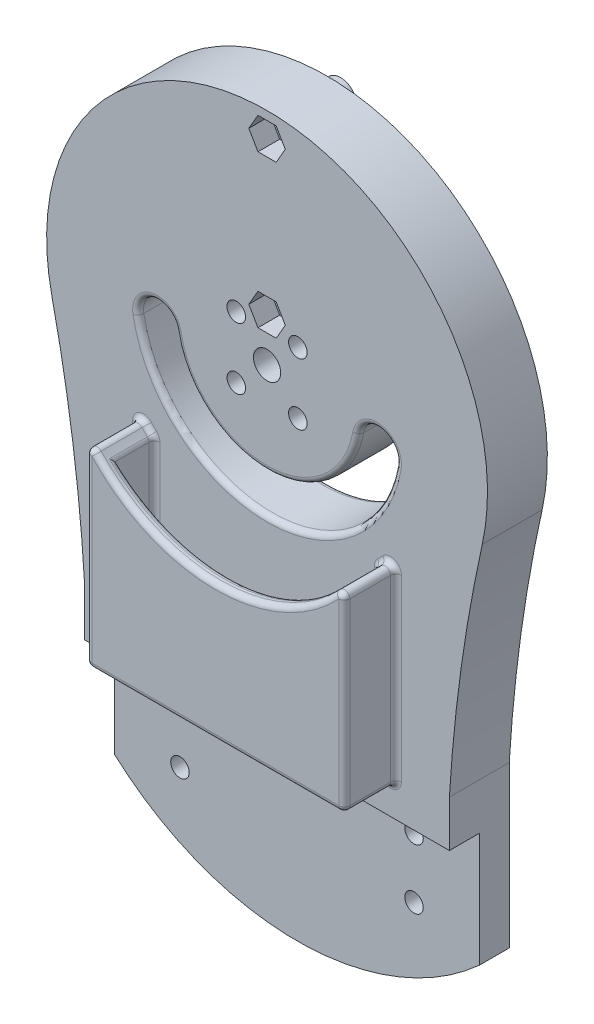
SolidWorks part; units mm, degrees
ref_plane "Front Plane" through (0, 0, 0) normal (0, 0, 1) x (1, 0, 0)
ref_plane "Top Plane" through (0, 0, 0) normal (0, 1, 0) x (1, 0, 0)
ref_plane "Right Plane" through (0, 0, 0) normal (1, 0, 0) x (0, 0, -1)
sketch "Sketch1" plane through (0, 0, 0) normal (0, 0, 1) x (1, 0, 0)
  line L0 (0, 0) -> (0, -52) construction
  line L1 (-33.5, -81.5) -> (33.5, -81.5)
  line L2 (-33.5, -81.5) -> (-33.5, -52)
  line L3 (-33.5, -52) -> (33.5, -52)
  line L4 (33.5, -81.5) -> (33.5, -52)
  line L5 (-33.5, -81.5) -> (33.5, -52) construction
  line L6 (-33.5, -52) -> (33.5, -81.5) construction
  line L7 (-55.7233, -60.5) -> (56.1574, -60.5) construction
  line L8 (0, 0) -> (-5.6569, -5.6569)
  circle A0 centre (0, 0) radius 40.5
  circle A1 centre (0, 0) radius 2.5
  arc A4 (-33.5, -52) -> (-39.5426, -8.7542) centre (-309.506, -68.5201) ccw
  arc A5 (33.5, -52) -> (39.5426, -8.7542) centre (309.506, -68.5201) cw
  arc A7 (-33.5, -81.5) -> (33.5, -81.5) centre (0, -44.3819) ccw
  circle A8 centre (0, 0) radius 8 construction
  circle A13 centre (-5.6569, -5.6569) radius 1.7
  circle A14 centre (-5.6569, 5.6569) radius 1.7
  circle A15 centre (5.6569, 5.6569) radius 1.7
  circle A16 centre (5.6569, -5.6569) radius 1.7
  point P4 (0, -66.75)
  point P37 (0, 0)
  dimension "D1" = 81
  dimension "D2" = 5
  dimension "D6" = 8.5
  dimension "D8" = 16
  dimension "D9" = 3.4
  dimension "D10" = 3.4
  dimension "D11" = 3.4
  dimension "D14" = 3.4
  dimension "D3" = 52
  dimension "D4" = 67
  dimension "D5" = 29.5
  dimension "D7" = 60.5
  dimension "D13" = 45
  dimension "D15" = 4
extrude "Boss-Extrude1" add sketch "Sketch1" along normal blind 5.5 and the other way blind 5.5 contours A0 A1 | L3 A0 | L1 L3 | L1 A7 region at (0, -66.75, 0) region at (0, -86.7143, 0) region at (0, -41.5421, 0) region at (-4.2786, 39.1212, 0)
sketch "Sketch2" plane through (0, 0, 5.5) normal (0, 0, 1) x (1, 0, 0)
  line L0 (-33.5, -81.5) -> (33.5, -81.5)
  line L1 (-33.5, -81.5) -> (-33.5, -60.5)
  line L2 (33.5, -81.5) -> (33.5, -60.5)
  line L3 (-33.5, -60.5) -> (33.5, -60.5)
  line L4 (-33.5, -81.5) -> (-33.5, -52) construction
  line L5 (33.5, -81.5) -> (33.5, -52) construction
  circle A0 centre (-21.5, -77.5) radius 1.7
  circle A1 centre (21.5, -77.5) radius 1.7
  circle A2 centre (21.5, -66.5) radius 1.7
  circle A3 centre (-21.5, -66.5) radius 1.7
  dimension "D2" = 3.4
  dimension "D3" = 3.4
  dimension "D4" = 3.4
  dimension "D5" = 3.4
  dimension "D8" = 6
  dimension "D1" = 21
  dimension "D6" = 12
  dimension "D7" = 12
  dimension "D9" = 11
  dimension "D10" = 67
  dimension "D11" = 81.5
  dimension "D12" = 33.5
extrude "Cut-Extrude1" cut sketch "Sketch2" against normal through all contours A0 | A3 | A2 | A1
sketch "Sketch3" plane through (0, 0, 5.5) normal (0, 0, 1) x (1, 0, 0)
  line L0 (33.5, -81.5) -> (33.5, -52) construction
  line L1 (-33.5, -95.5) -> (33.5, -95.5)
  line L2 (-33.5, -95.5) -> (-33.5, -60.5)
  line L3 (-33.5, -60.5) -> (33.5, -60.5)
  line L4 (33.5, -95.5) -> (33.5, -60.5)
  dimension "D1" = 35
  dimension "D2" = 60.5
  dimension "D3" = 33.5
  dimension "D4" = 67
extrude "Cut-Extrude2" cut sketch "Sketch3" against normal blind 5.5
sketch "Sketch4" plane through (0, 0, -5.5) normal (0, 0, -1) x (-1, 0, 0)
  circle A0 centre (0, 0) radius 4.7825 construction
  circle A2 centre (0, 36) radius 1.7
  circle A3 centre (0, 8) radius 1.7
  circle A5 centre (0, 36) radius 4 construction
  dimension "D4" = 3.4
  dimension "D5" = 3.4
  dimension "D6" = 8
  dimension "D1" = 8
  dimension "D2" = 28
extrude "Cut-Extrude3" cut sketch "Sketch4" against normal through all
sketch "Sketch5" plane through (0, 0, 5.5) normal (0, 0, 1) x (1, 0, 0)
  line L0 (-1.675, 10.9012) -> (1.675, 10.9012)
  line L1 (1.675, 10.9012) -> (3.35, 8)
  line L2 (-1.675, 10.9012) -> (-3.35, 8)
  line L3 (-3.35, 8) -> (-1.675, 5.0988)
  line L4 (-1.675, 5.0988) -> (1.675, 5.0988)
  line L5 (1.675, 5.0988) -> (3.35, 8)
  line L6 (-1.675, 10.9012) -> (0, 8) construction
  line L7 (0, 8) -> (1.675, 10.9012) construction
  line L8 (0, 8) -> (-1.675, 5.0988) construction
  line L9 (0, 8) -> (1.675, 5.0988) construction
  line L10 (-3.35, 8) -> (3.35, 8) construction
  line L11 (-9.1797, 22) -> (14.4985, 22) construction
  line L12 (-1.675, 38.9012) -> (1.675, 38.9012)
  line L13 (-3.35, 36) -> (-1.675, 38.9012)
  line L14 (-1.675, 33.0988) -> (-3.35, 36)
  line L15 (-1.675, 33.0988) -> (1.675, 33.0988)
  line L16 (1.675, 33.0988) -> (3.35, 36)
  line L17 (1.675, 38.9012) -> (3.35, 36)
  circle A0 centre (0, 8) radius 3.35 construction
  circle A1 centre (0, 36) radius 3.35 construction
  dimension "D1" = 6.7
  dimension "D6" = 6.7
  dimension "D2" = 60
  dimension "D3" = 60
  dimension "D4" = 60
  dimension "D5" = 14
extrude "Cut-Extrude4" cut sketch "Sketch5" against normal blind 4 contours L5 L1 L0 L2 L3 L4 | L16 L17 L12 L13 L14 L15
ref_plane "Plane1" through (33.5, -81.5, -5.5) normal (0, 0, 1) x (1, 0, 0)
sketch "Sketch6" plane through (33.5, -81.5, -5.5) normal (0, 0, 1) x (1, 0, 0)
  line L0 (-26.1681, 90.058) -> (-29.5181, 84.2557) construction
  line L1 (-26.1681, 84.2557) -> (-29.5181, 90.058) construction
  line L2 (-24.4931, 87.1569) -> (-31.1931, 87.1569) construction
  line L3 (-26.1681, 90.058) -> (-24.4931, 87.1569)
  line L4 (-24.4931, 87.1569) -> (-26.1681, 84.2557)
  line L5 (-26.1681, 84.2557) -> (-29.5181, 84.2557)
  line L6 (-29.5181, 84.2557) -> (-31.1931, 87.1569)
  line L7 (-31.1931, 87.1569) -> (-29.5181, 90.058)
  line L8 (-29.5181, 90.058) -> (-26.1681, 90.058)
  line L9 (-27.8431, 75.8431) -> (-39.1569, 87.1569) construction
  line L10 (-27.8431, 87.1569) -> (-39.1569, 75.8431) construction
  line L11 (-35.8069, 87.1569) -> (-42.5069, 87.1569) construction
  line L12 (-39.1569, 87.1569) -> (-37.4819, 90.058) construction
  line L13 (-39.1569, 87.1569) -> (-40.8319, 90.058) construction
  line L14 (-39.1569, 87.1569) -> (-37.4819, 84.2557) construction
  line L15 (-39.1569, 87.1569) -> (-40.8319, 84.2557) construction
  line L22 (-37.4819, 84.2557) -> (-35.8069, 87.1569)
  line L23 (-35.8069, 87.1569) -> (-37.4819, 90.058)
  line L24 (-37.4819, 90.058) -> (-40.8319, 90.058)
  line L25 (-40.8319, 90.058) -> (-42.5069, 87.1569)
  line L26 (-42.5069, 87.1569) -> (-40.8319, 84.2557)
  line L27 (-40.8319, 84.2557) -> (-37.4819, 84.2557)
  line L28 (-39.1569, 79.1931) -> (-42.058, 77.5181)
  line L29 (-36.2557, 77.5181) -> (-39.1569, 79.1931)
  line L30 (-36.2557, 74.1681) -> (-36.2557, 77.5181)
  line L31 (-39.1569, 72.4931) -> (-36.2557, 74.1681)
  line L32 (-42.058, 74.1681) -> (-39.1569, 72.4931)
  line L33 (-42.058, 77.5181) -> (-42.058, 74.1681)
  line L34 (-27.8431, 72.4931) -> (-30.7443, 74.1681)
  line L35 (-24.942, 74.1681) -> (-27.8431, 72.4931)
  line L36 (-24.942, 77.5181) -> (-24.942, 74.1681)
  line L37 (-27.8431, 79.1931) -> (-24.942, 77.5181)
  line L38 (-30.7443, 77.5181) -> (-27.8431, 79.1931)
  line L39 (-30.7443, 74.1681) -> (-30.7443, 77.5181)
  line L40 (-10.325, 12.0988) -> (-13.675, 17.9012) construction
  line L41 (-10.325, 17.9012) -> (-13.675, 12.0988) construction
  line L42 (-8.65, 15) -> (-15.35, 15) construction
  line L43 (-10.325, 6.9012) -> (-13.675, 1.0988) construction
  line L44 (-10.325, 1.0988) -> (-13.675, 6.9012) construction
  line L45 (-8.65, 4) -> (-15.35, 4) construction
  line L46 (-33.5, 21.3433) -> (-33.5, -3.4407) construction
  line L47 (-8.65, 4) -> (-10.325, 6.9012)
  line L48 (-10.325, 6.9012) -> (-13.675, 6.9012)
  line L49 (-13.675, 6.9012) -> (-15.35, 4)
  line L50 (-15.35, 4) -> (-13.675, 1.0988)
  line L51 (-13.675, 1.0988) -> (-10.325, 1.0988)
  line L52 (-10.325, 1.0988) -> (-8.65, 4)
  line L53 (-10.325, 17.9012) -> (-13.675, 17.9012)
  line L54 (-13.675, 17.9012) -> (-15.35, 15)
  line L55 (-15.35, 15) -> (-13.675, 12.0988)
  line L56 (-13.675, 12.0988) -> (-10.325, 12.0988)
  line L57 (-10.325, 12.0988) -> (-8.65, 15)
  line L58 (-8.65, 15) -> (-10.325, 17.9012)
  line L59 (-53.325, 1.0988) -> (-56.675, 1.0988)
  line L60 (-51.65, 4) -> (-53.325, 1.0988)
  line L61 (-53.325, 6.9012) -> (-51.65, 4)
  line L62 (-56.675, 6.9012) -> (-53.325, 6.9012)
  line L63 (-58.35, 4) -> (-56.675, 6.9012)
  line L64 (-56.675, 1.0988) -> (-58.35, 4)
  line L65 (-56.675, 12.0988) -> (-58.35, 15)
  line L66 (-53.325, 12.0988) -> (-56.675, 12.0988)
  line L67 (-51.65, 15) -> (-53.325, 12.0988)
  line L68 (-53.325, 17.9012) -> (-51.65, 15)
  line L69 (-56.675, 17.9012) -> (-53.325, 17.9012)
  line L70 (-58.35, 15) -> (-56.675, 17.9012)
  circle A0 centre (-33.5, 81.5) radius 8 construction
  circle A1 centre (-27.8431, 87.1569) radius 3.35 construction
  circle A3 centre (-39.1569, 87.1569) radius 3.35 construction
  circle A4 centre (-12, 15) radius 3.35 construction
  circle A5 centre (-12, 4) radius 3.35 construction
  circle A7 centre (-55, 4) radius 3.35 construction
  dimension "D1" = 6.7
  dimension "D5" = 6.7
  dimension "D9" = 6.7
  dimension "D10" = 6.7
  dimension "D11" = 60
  dimension "D17" = 6.7
  dimension "D2" = 60
  dimension "D3" = 60
  dimension "D4" = 60
  dimension "D6" = 60
  dimension "D7" = 60
  dimension "D8" = 60
  dimension "D12" = 60
  dimension "D13" = 60
  dimension "D14" = 60
  dimension "D15" = 21.5
  dimension "D16" = 43
extrude "Cut-Extrude7" cut sketch "Sketch6" along normal blind 3 contours L8 L3 L4 L5 L6 L7 | L27 L22 L23 L24 L25 L26 | L28 L33 L32 L31 L30 L29 | L34 L39 L38 L37 L36 L35 | L59 L64 L63 L62 L61 L60 | L65 L70 L69 L68 L67 L66 | L52 L47 L48 L49 L50 L51 | L58 L53 L54 L55 L56 L57
sketch "Sketch7" plane through (0, 0, -5.5) normal (0, 0, -1) x (-1, 0, 0)
  circle A0 centre (0, 8) radius 3
  circle A1 centre (0, 36) radius 3
  circle A2 centre (0, 36) radius 1.7
  circle A3 centre (0, 8) radius 1.7
  dimension "D1" = 6
  dimension "D2" = 6
  dimension "D3" = 3.4
  dimension "D4" = 3.4
extrude "Boss-Extrude2" add sketch "Sketch7" along normal blind 2.5
sketch "Sketch9" plane through (0, 0, -5.5) normal (0, 0, -1) x (-1, 0, 0)
  line L0 (-2.7293, 4) -> (2.7293, 4)
  line L1 (-11.5, 2.2) -> (11.5, 2.2)
  line L2 (-11.5, 2.2) -> (-11.5, -2.2)
  line L3 (-11.5, -2.2) -> (11.5, -2.2)
  line L4 (11.5, 2.2) -> (11.5, -2.2)
  line L5 (-11.5, 2.2) -> (11.5, -2.2) construction
  line L6 (-11.5, -2.2) -> (11.5, 2.2) construction
  circle A0 centre (0, 0) radius 4.8424
  circle A1 centre (0, 0) radius 2.5
  dimension "D3" = 4
  dimension "D1" = 4.4
  dimension "D2" = 23
extrude "Boss-Extrude3" add sketch "Sketch9" along normal blind 8 contours A0 L1 L2 L3 | A0 L3 L4 L1 | A1 L3 A0 L1 | A1 L1 A0 L3 | A1 L1 A0 | A1 L3 A0 region at (0, 3.0636, -5.5) region at (8.0833, 0, -5.5) region at (3.3746, 0, -5.5) region at (-3.3746, 0, -5.5) region at (-8.0833, 0, -5.5) region at (0, -3.3158, -5.5)
sketch "Sketch10" plane through (0, 0, -13.5) normal (0, 0, -1) x (-1, 0, 0)
  line L0 (4.3138, 2.2) -> (11.5, 2.2) construction
  line L1 (-14.44, 28.2) -> (14.4114, 28.2) construction
  line L2 (-14.44, 22.2) -> (14.8305, 22.2) construction
  line L3 (4.3138, 2.2) -> (11.5, 2.2) construction
  line L4 (-13.3353, 25.2) -> (9.1762, 25.2) construction
  circle A1 centre (0, 0) radius 25.2 construction
  dimension "D1" = 20
  dimension "D2" = 26
  dimension "D3" = 3
sketch "Sketch11" plane through (0, 0, -5.5) normal (0, 0, -1) x (-1, 0, 0)
  line L0 (-24, 0) -> (24, 0)
  line L1 (0, 0) -> (0, -17) construction
  circle A0 centre (0, 0) radius 17
  circle A1 centre (0, 0) radius 24
  circle A3 centre (0, 0) radius 20.5 construction
  circle A5 centre (-20.199, -3.5) radius 3.5
  circle A6 centre (20.199, -3.5) radius 3.5
  dimension "D1" = 34
  dimension "D2" = 7
  dimension "D3" = 3.5
  dimension "D5" = 7
extrude "Cut-Extrude8" cut sketch "Sketch11" against normal through all contours A1 A6 A0 A5 | A5 | A6 A1 region at (20.199, -3.5, -5.5) region at (19.8548, -7.5031, -5.5) region at (-20.199, -3.5, -5.5)
sketch "Sketch12" plane through (0, 0, 5.5) normal (0, 0, 1) x (1, 0, 0)
  line L0 (-23.699, -3.5) -> (-23.699, -55)
  line L1 (23.699, -3.5) -> (23.699, -55)
  line L2 (23.699, -55) -> (-23.699, -55)
  line L3 (0, 0) -> (0, -30) construction
  line L4 (0, -30) -> (0, -55)
  circle A0 centre (0, 0) radius 30
  arc A1 (-16.7504, -2.9024) -> (-23.6476, -4.0976) centre (-20.199, -3.5) ccw construction
  arc A2 (23.6476, -4.0976) -> (16.7504, -2.9024) centre (20.199, -3.5) ccw construction
  circle A3 centre (-20.199, -3.5) radius 3.5 construction
  circle A4 centre (20.199, -3.5) radius 3.5 construction
  dimension "D1" = 60
  dimension "D2" = 47.398
  dimension "D3" = 25
extrude "Boss-Extrude4" add sketch "Sketch12" along normal blind 9.5 contours A0 L0 L2 L4 | A0 L4 L2 L1 region at (-12.61, -40.552, 5.5) region at (12.61, -40.552, 5.5)
fillet "Fillet1" radius 1 8 edges at (23.699, -18.3945, 10.25) (-23.699, -18.3945, 10.25) (23.699, -55, 10.25) (-23.699, -55, 10.25) (0, -30, 15) (23.699, -36.6972, 15) (-23.699, -36.6972, 15) (0, -55, 15)
sketch "Sketch13" plane through (0, -55, 0) normal (0, -1, 0) x (1, 0, 0)
  line L0 (33.5, 5.5) -> (-33.5, 5.5) construction
  line L1 (-20.699, 5.5) -> (20.699, 5.5)
  line L2 (-20.699, 5.5) -> (-20.699, 12.5)
  line L3 (-20.699, 12.5) -> (20.699, 12.5)
  line L4 (20.699, 5.5) -> (20.699, 12.5)
  line L5 (-23.699, 5.5) -> (-23.699, 14) construction
  line L6 (22.699, 15) -> (-22.699, 15) construction
  line L7 (23.699, 14) -> (23.699, 5.5) construction
  dimension "D1" = 3
  dimension "D2" = 2.5
  dimension "D3" = 3
extrude "Cut-Extrude9" cut sketch "Sketch13" against normal through all contours L2 L1 L4 L3
fillet "Fillet2" radius 1 26 edges at (-21.3425, -21.0831, 5.5) (-23.0649, -20.1823, 5.5) (-23.699, -37.5565, 5.5) (-23.4061, -54.7071, 5.5) (21.3425, -21.0831, 5.5) (23.0649, -20.1823, 5.5) (23.699, -37.5565, 5.5) (23.4061, -54.7071, 5.5) (20.699, -21.7152, 9) (0, -30, 12.5) (-20.699, -21.7152, 9) (-20.699, -55, 9) (20.699, -55, 9) (0, -55, 12.5) (-21.699, -55, 5.5) (21.699, -55, 5.5) (20.699, -38.3576, 5.5) (-20.699, -38.3576, 5.5) (20.7966, -0.0514, -5.5) (0, -17, -5.5) (-20.7966, -0.0514, -5.5) (20.7966, -0.0514, 5.5) (0, -17, 5.5) (-20.7966, -0.0514, 5.5) (0, -24, -5.5) (0, -24, 5.5)
sketch "Sketch14" plane through (0, 0, -5.5) normal (0, 0, -1) x (-1, 0, 0)
  line L0 (0, 0) -> (-13.4234, -7.75)
  line L1 (0, 0) -> (0, -15.5) construction
  line L2 (0, 0) -> (13.4234, -7.75)
  circle A0 centre (0, 0) radius 15.5
  circle A1 centre (0, 0) radius 12.5
  dimension "D1" = 31
  dimension "D2" = 3
  dimension "D3" = 60
  dimension "D4" = 60
extrude "Boss-Extrude5" add sketch "Sketch14" along normal blind 20 contours L1 A1 L0 A0 | A1 L1 A0 L2 region at (6.7101, -11.6222, -5.5) region at (-6.7101, -11.6222, -5.5)
sketch "Sketch15" plane through (0, 0, -5.5) normal (0, 0, -1) x (-1, 0, 0)
  line L0 (0, 0) -> (0, 18.9061) construction
  line L1 (0, 0) -> (-32.3633, 3.9737)
  line L2 (0, 0) -> (-28.6359, 14.5907)
  circle A0 centre (0, 0) radius 12.5
  circle A1 centre (0, 0) radius 30
  circle A2 centre (0, 0) radius 28
  circle A3 centre (0, 0) radius 14.5
  dimension "D1" = 60
  dimension "D2" = 25
  dimension "D5" = 2
  dimension "D6" = 2
  dimension "D3" = 63
  dimension "D4" = 83
extrude "Boss-Extrude6" add sketch "Sketch15" along normal blind 4 contours A2 L2 A1 L1 | L2 A3 L1 A0 region at (12.8682, 3.9342, -5.5) region at (27.6032, 8.4391, -5.5)
sketch "Sketch16" plane through (0, 0, -9.5) normal (0, 0, -1) x (-1, 0, 0)
  line L0 (-29.7764, 3.6561) -> (0, 0)
  line L1 (0, 0) -> (-26.7302, 13.6197)
  circle A0 centre (0, 0) radius 12.5
  circle A1 centre (0, 0) radius 30
  arc M3 (-27.7913, 3.4123) -> (-24.9482, 12.7117) centre (0, 0) cw
  line M4 (-24.9482, 12.7117) -> (-26.7302, 13.6197)
  arc M5 (-26.7302, 13.6197) -> (-29.7764, 3.6561) centre (0, 0) ccw
  line M6 (-29.7764, 3.6561) -> (-27.7913, 3.4123)
  dimension "D1" = 60
  dimension "D2" = 25
extrude "Boss-Extrude7" add sketch "Sketch16" along normal blind 2 contours A0 L1 L0 M3 | M6 M3 M4 M5 region at (27.6032, 8.4391, -9.5) region at (20.2077, 6.1781, -9.5)
